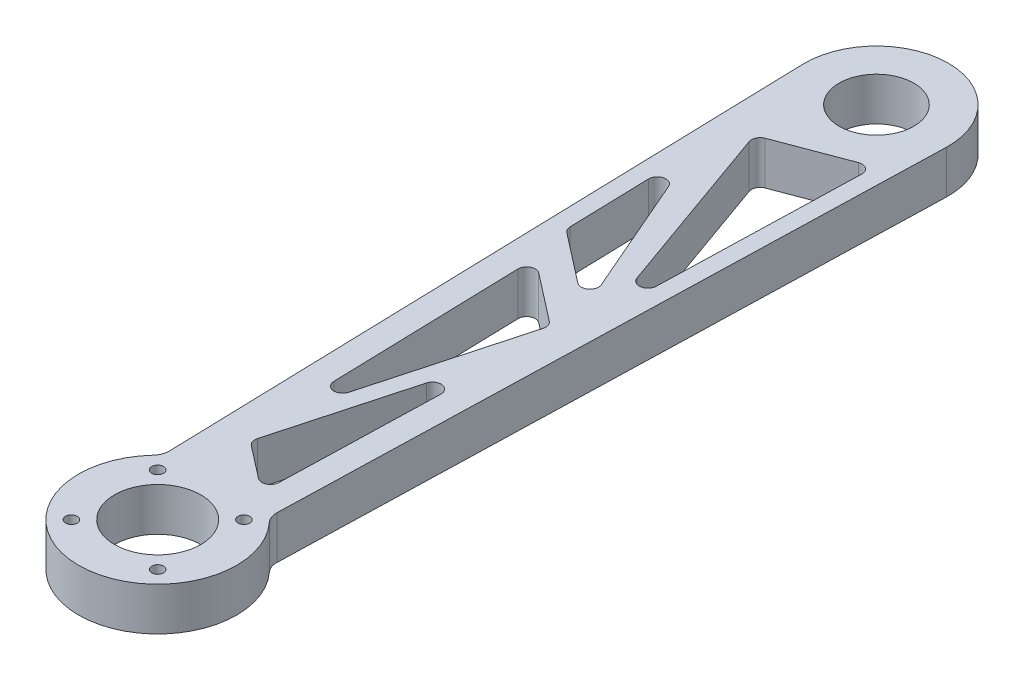
SolidWorks part; units mm, degrees
material "1060 合金"
ref_plane "前视基准面" through (0, 0, 0) normal (0, 0, 1) x (1, 0, 0)
ref_plane "上视基准面" through (0, 0, 0) normal (0, 1, 0) x (1, 0, 0)
ref_plane "右视基准面" through (0, 0, 0) normal (1, 0, 0) x (0, 0, -1)
sketch "草图1" plane through (0, 0, 0) normal (0, 1, 0) x (1, 0, 0)
  line L0 (0, 0) -> (0, 250) construction
  line L1 (-17.9929, -0.504) -> (-24.9902, 249.3)
  line L2 (17.9929, -0.504) -> (24.9902, 249.3)
  line L3 (-11.9953, -0.336) -> (-18.9926, 249.468) construction
  line L4 (11.9953, -0.336) -> (18.9926, 249.468) construction
  line L5 (-16.4444, 158.5) -> (15.7446, 133.5146) construction
  line L6 (15.7446, 133.5146) -> (18.4752, 231) construction
  line L7 (18.4752, 231) -> (-18.0888, 217.2024) construction
  line L8 (-18.0888, 217.2024) -> (-16.4444, 158.5) construction
  line L9 (15.7446, 133.5146) -> (-18.0888, 217.2024) construction
  line L10 (18.5259, 134.639) -> (-15.3075, 218.3268) construction
  line L11 (12.9633, 132.3901) -> (-20.8701, 216.0779) construction
  line L12 (-16.4444, 158.5) -> (-17.7049, 203.5)
  line L13 (-17.7049, 203.5) -> (11.0289, 137.1749)
  line L14 (11.0289, 137.1749) -> (-16.4444, 158.5)
  line L15 (15.9543, 141) -> (18.4752, 231)
  line L16 (-15.3075, 218.3268) -> (-18.4322, 226.0559) construction
  line L17 (18.4752, 231) -> (-12, 219.5)
  line L18 (-12, 219.5) -> (15.9543, 141)
  circle A0 centre (0, 250) radius 25 construction
  circle A1 centre (0, 0) radius 18 construction
  circle A2 centre (0, 0) radius 5.05
  circle A3 centre (0, 250) radius 13
  arc A4 (-17.9929, -0.504) -> (17.9929, -0.504) centre (0, 0) ccw
  arc A5 (-24.9902, 249.3) -> (24.9902, 249.3) centre (0, 250) cw
  arc A6 (-18.9926, 249.468) -> (18.9926, 249.468) centre (0, 250) cw construction
  arc A7 (-11.9953, -0.336) -> (11.9953, -0.336) centre (0, 0) ccw construction
  dimension "D2" = 50
  dimension "D3" = 36
  dimension "D4" = 10.1
  dimension "D5" = 26
  dimension "D1" = 250
  dimension "D9" = 19
  dimension "D10" = 30.5
  dimension "D11" = 16
  dimension "D12" = 45
  dimension "D13" = 90
  dimension "D14" = 12
  dimension "D6" = 6
  dimension "D7" = 3
  dimension "D8" = 3
extrude "凸台-拉伸1" add sketch "草图1" along normal blind 15
fillet "圆角1" radius 3 6 edges at (18.4752, 7.5, -231) (-12, 7.5, -219.5) (-17.7049, 7.5, -203.5) (-16.4444, 7.5, -158.5) (15.9543, 7.5, -141) (11.0289, 7.5, -137.1749)
sketch "草图2" plane through (0, 15, 0) normal (0, 1, 0) x (1, 0, 0)
  line L0 (0, 250) -> (-15, 250) construction
  circle A0 centre (-15, 250) radius 2
  dimension "D2" = 4
  dimension "D1" = 15
extrude "切除-拉伸1" [suppressed] cut sketch "草图2" against normal through all
pattern_circular "阵列(圆周)1" [suppressed] count 3 over 360 reverse direction yes of bodies 107
sketch "草图3" plane through (0, 15, 0) normal (0, 1, 0) x (1, 0, 0)
  line L0 (0, 250) -> (14.25, 250) construction
  circle A0 centre (14.25, 250) radius 2
  dimension "D2" = 4
  dimension "D1" = 14.25
extrude "切除-拉伸2" [suppressed] cut sketch "草图3" against normal through all
pattern_circular "阵列(圆周)2" [suppressed] count 3 over 360 of bodies 109
sketch "草图4" plane through (0, 15, 0) normal (0, 1, 0) x (1, 0, 0)
  line L2 (8.9965, -0.252) -> (15.9937, 249.552)
  line L3 (8.9965, -0.252) -> (15.9937, 249.552) construction
  line L4 (-13.0503, 144.4724) -> (12.4949, 124.6439)
  line L5 (-15.9937, 249.552) -> (-8.9965, -0.252)
  line L6 (-15.9937, 249.552) -> (-8.9965, -0.252) construction
  line L7 (-15.3248, 157.6309) -> (1.7846, 144.3504) construction
  line L8 (12.4949, 124.6439) -> (9.7421, 26.3657)
  line L9 (9.7421, 26.3657) -> (-10.1751, 41.8256)
  line L10 (-10.1751, 41.8256) -> (-13.0503, 144.4724)
  dimension "D3" = 9
  dimension "D1" = 9
  dimension "D2" = 9
extrude "切除-拉伸3" cut sketch "草图4" against normal through all
fillet "圆角2" radius 3 3 edges at (9.7421, 7.5, -26.3657) (-10.1751, 7.5, -41.8256) (-13.0503, 7.5, -144.4724)
sketch "草图5" plane through (0, 15, 0) normal (0, 1, 0) x (1, 0, 0)
  circle A0 centre (0, 0) radius 27.5
  circle A1 centre (0, 0) radius 5.05
  dimension "D1" = 55
extrude "凸台-拉伸2" add sketch "草图5" against normal up to surface (15 mm away) up to face at (-1.8624, 0, -78.5335)
fillet "圆角3" radius 6 2 edges at (-18.5751, 7.5, -20.2785) (18.5751, 7.5, -20.2785)
sketch "草图6" plane through (0, 15, 0) normal (0, 1, 0) x (1, 0, 0)
  line L0 (12.4949, 124.6439) -> (-10.1751, 41.8256) construction
  line L1 (-12.8725, 138.1249) -> (-10.2148, 43.2424) construction
  line L2 (9.6014, 125.4359) -> (-13.0687, 42.6176)
  line L3 (15.3885, 123.8518) -> (-7.2816, 41.0335)
  line L4 (-7.2816, 41.0335) -> (-7.6098, 39.8344)
  line L5 (-7.6098, 39.8344) -> (-13.0687, 42.6176)
  line L6 (9.6014, 125.4359) -> (9.9296, 126.6351)
  line L7 (9.9296, 126.6351) -> (15.3885, 123.8518)
  line L8 (-9.0555, 40.9565) -> (5.0694, 29.9927) construction
  line L9 (12.4949, 124.6439) -> (-8.0342, 140.5788) construction
  dimension "D1" = 3
  dimension "D2" = 3
extrude "凸台-拉伸3" add sketch "草图6" against normal up to surface (15 mm away) up to face at (-1.8624, 0, -78.5335)
fillet "圆角4" radius 3 4 edges at (12.1404, 7.5, -111.9858) (-10.4638, 7.5, -52.1336) (9.9296, 7.5, -126.6351) (-7.6098, 7.5, -39.8344)
sketch "草图7" plane through (0, 15, 0) normal (0, 1, 0) x (1, 0, 0)
  line L1 (15, 15) -> (-15, 15) construction
  line L2 (15, 15) -> (15, -15) construction
  line L3 (15, -15) -> (-15, -15) construction
  line L4 (-15, 15) -> (-15, -15) construction
  circle A0 centre (0, 0) radius 5.05 construction
  circle A1 centre (15, 15) radius 2.05
  circle A2 centre (-15, 15) radius 2.05
  circle A3 centre (-15, -15) radius 2.05
  circle A5 centre (15, -15) radius 2.05
  dimension "D2" = 15
  dimension "D4" = 4.1
  dimension "D1" = 30
  dimension "D3" = 15
extrude "切除-拉伸4" cut sketch "草图7" against normal through all
sketch "草图8" plane through (0, 15, 0) normal (0, 1, 0) x (1, 0, 0)
  circle A0 centre (0, 0) radius 15
  dimension "D1" = 30
extrude "切除-拉伸5" cut sketch "草图8" against normal through all
